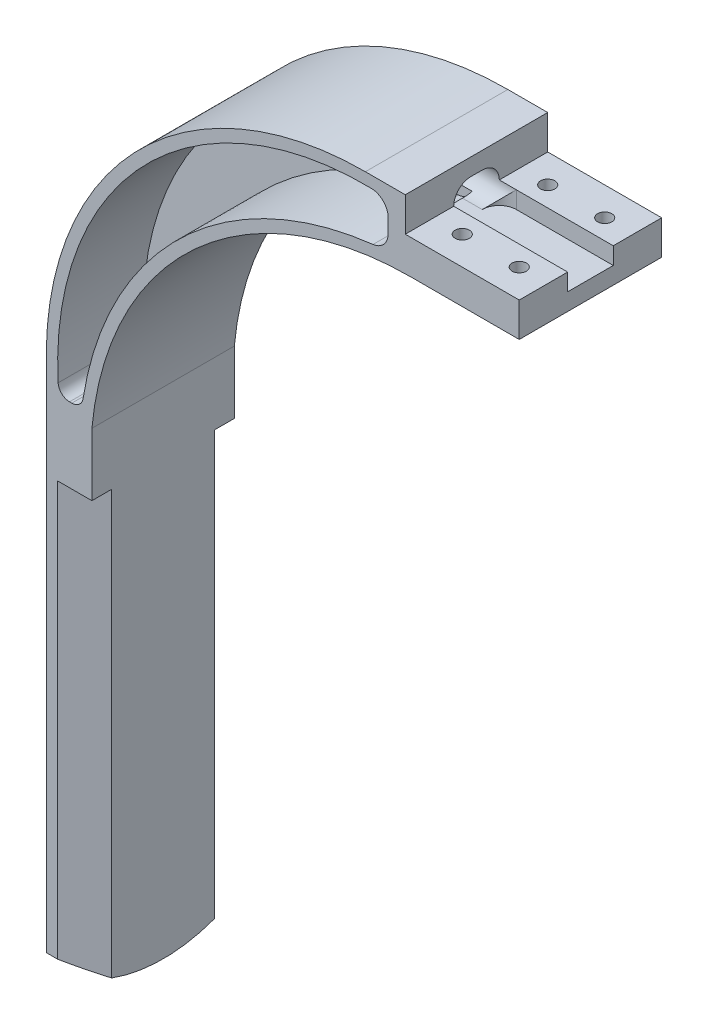
SolidWorks part; units mm, degrees
material "Сплав 2024"
ref_plane "Спереди" through (0, 0, 0) normal (0, 0, 1) x (1, 0, 0)
ref_plane "Сверху" through (0, 0, 0) normal (0, 1, 0) x (1, 0, 0)
ref_plane "Справа" through (0, 0, 0) normal (1, 0, 0) x (0, 0, -1)
sketch "Эскиз1" plane through (0, 0, 0) normal (0, 0, 1) x (1, 0, 0)
  line L0 (0, 0) -> (0, 95)
  line L1 (0, 0) -> (8, 0)
  line L2 (-20.7345, 150) -> (144.5665, 150) construction
  line L3 (83, 163.3115) -> (83, 122.0175) construction
  line L4 (8, 0) -> (8, 87)
  line L6 (83, 150) -> (56, 150)
  line L7 (83, 150) -> (83, 138)
  line L8 (83, 138) -> (64, 138)
  arc A0 (64, 138) -> (8, 87) centre (64, 81.7549) ccw
  arc A1 (56, 150) -> (0, 95) centre (56, 93.9909) ccw
  dimension "D1" = 95
  dimension "D2" = 87
  dimension "D3" = 150
  dimension "D4" = 83
  dimension "D5" = 8
  dimension "D6" = 12
  dimension "D7" = 27
  dimension "D8" = 19
extrude "Бобышка-Вытянуть1" add sketch "Эскиз1" along normal blind 25
sketch "Эскиз2" plane through (0, 0, 25) normal (0, 0, 1) x (1, 0, 0)
  line L1 (83, 150) -> (63, 150)
  line L2 (83, 150) -> (83, 144)
  line L3 (83, 144) -> (63, 144)
  line L4 (63, 150) -> (63, 144)
  dimension "D1" = 20
  dimension "D2" = 6
extrude "Вырез-Вытянуть1" cut sketch "Эскиз2" against normal through all
sketch "Эскиз5" plane through (0, 0, 0) normal (0, -1, 0) x (1, 0, 0)
  line L0 (8, 3.4641) -> (2, 0)
  line L1 (8, 25) -> (8, 0) construction
  line L3 (2, 0) -> (8, 0)
  line L4 (8, 0) -> (8, 3.4641)
  line L5 (0, 25) -> (0, 0) construction
  line L6 (8, 12.5) -> (7.5, 12.5) construction
  line L7 (8, 25) -> (8, 0) construction
  line L8 (8, 25) -> (8, 21.5359)
  line L9 (2, 25) -> (8, 25)
  line L10 (8, 21.5359) -> (2, 25)
  line L11 (0, 0) -> (8, 0) construction
  dimension "D1" = 2
  dimension "D2" = 60
extrude "Вырез-Вытянуть2" cut sketch "Эскиз5" against normal blind 76
sketch "Эскиз6" plane through (0, 0, 0) normal (-1, 0, 0) x (0, 0, 1)
  line L0 (12.5, 0) -> (12.5, 16.6862) construction
  line L1 (25, 0) -> (0, 0) construction
  line L2 (12.5, -11.9161) -> (12.5, 92.5) construction
  line L3 (10, -11.9161) -> (10, 92.5)
  line L4 (15, -11.9161) -> (15, 92.5)
  line L5 (25, 95) -> (0, 95) construction
  arc A0 (10, -11.9161) -> (15, -11.9161) centre (12.5, -11.9161) ccw
  arc A1 (15, 92.5) -> (10, 92.5) centre (12.5, 92.5) ccw
  point P7 (12.5, 40.292)
  dimension "D1" = 5
extrude "Вырез-Вытянуть4" cut sketch "Эскиз6" against normal blind 5
sketch "Эскиз3" plane through (0, 0, 25) normal (0, 0, -1) x (-1, 0, 0)
  line L0 (-60, 147.8517) -> (-60, 139.8625)
  line L1 (-63, 150) -> (-63, 144) construction
  line L2 (-6.2158, 89.0676) -> (-2.2158, 89.0676)
  arc A4 (-60, 147.8517) -> (-2.2158, 89.0676) centre (-56, 93.9909) cw
  arc A5 (-60, 139.8625) -> (-6.2158, 89.0676) centre (-64, 81.7549) cw
  arc A6 (0, 95) -> (-56, 150) centre (-56, 93.9909) ccw construction
  arc A7 (-8, 87) -> (-64, 138) centre (-64, 81.7549) ccw construction
  dimension "D1" = 2
  dimension "D2" = 2
  dimension "D3" = 3
  dimension "D4" = 4
extrude "Вырез-Вытянуть3" cut sketch "Эскиз3" along normal up to surface (15 mm away) up to face at (2.5, 46.25, 10)
fillet "Скругление3" radius 2 2 edges at (6.2158, 89.0676, 17.5) (2.2158, 89.0676, 20)
fillet "Скругление4" radius 3 2 edges at (60, 147.8517, 17.5) (60, 139.8625, 17.5)
ref_plane "Плоскость1" through (0, 10, 0) normal (0, 1, 0) x (1, 0, 0)
sketch "Эскиз8" plane through (0, 10, 0) normal (0, 1, 0) x (1, 0, 0)
  line L0 (0, -2) -> (1.5, -2)
  line L1 (0, -12.5) -> (0, 0) construction
  line L2 (1.5, -2) -> (1.5, -3)
  line L3 (3.5, -4) -> (5.5, -4)
  line L4 (5.5, -4) -> (5.5, -8)
  line L5 (5.5, -8) -> (0, -8)
  line L6 (0, -8) -> (0, -2)
  line L7 (56, 0) -> (0, 0) construction
  line L8 (2.0115, -10) -> (0, -10) construction
  line L9 (1.5, -3) -> (3.5, -3)
  line L10 (3.5, -3) -> (3.5, -4)
  line L11 (8, -25) -> (8, 0) construction
  line L12 (8, -12.5) -> (6.1534, -12.5) construction
  line L13 (3.5, -22) -> (3.5, -21)
  line L14 (1.5, -22) -> (3.5, -22)
  line L15 (0, -17) -> (0, -23)
  line L16 (5.5, -17) -> (0, -17)
  line L17 (5.5, -21) -> (5.5, -17)
  line L18 (3.5, -21) -> (5.5, -21)
  line L19 (1.5, -23) -> (1.5, -22)
  line L20 (0, -23) -> (1.5, -23)
  dimension "D1" = 2
  dimension "D2" = 2
  dimension "D3" = 4
  dimension "D4" = 1
  dimension "D5" = 1.5
  dimension "D6" = 2
  dimension "D7" = 2.5
extrude "Вырез-Вытянуть6" cut sketch "Эскиз8" along normal blind 75
sketch "Эскиз9" plane through (0, 144, 0) normal (0, 1, 0) x (1, 0, 0)
  line L0 (83, 0) -> (63, -25) construction
  line L1 (83, 0) -> (83, -25) construction
  line L2 (68, -5) -> (78, -5) construction
  line L3 (68, -5) -> (68, -20) construction
  line L4 (68, -20) -> (78, -20) construction
  line L5 (78, -5) -> (78, -20) construction
  line L6 (68, -5) -> (78, -20) construction
  line L7 (68, -20) -> (78, -5) construction
  line L8 (63, 0) -> (83, 0) construction
  point P4 (73, -12.5)
  dimension "D1" = 5
  dimension "D2" = 5
hole_wizard "Отверстие обработанное метчиком M3x0.51" positions "Эскиз11" profile "Эскиз10" tap size "M3x0.5" standard "Ansi Metric" end condition up to next
sketch "Эскиз11" plane through (0, 144, 0) normal (0, 1, 0) x (1, 0, 0)
  point P0 (68, -5)
  point P3 (78, -5)
  point P6 (78, -20)
  point P9 (68, -20)
sketch "Эскиз10" plane through (68, 144, 5) normal (1, 0, 0) x (0, 0, 1)
  line L0 (0, 0) -> (0, 6)
  line L1 (0, 6) -> (1.25, 6)
  line L2 (1.25, 6) -> (1.25, 0)
  line L5 (1.25, 0) -> (0, 0)
  line L11 (0, -6.35) -> (0, 107.95) construction
  dimension "Диаметр резьбы" = 2.5
  dimension "Глубина проходного сверла" = 6
sketch "Эскиз12" plane through (0, 0, 0) normal (-1, 0, 0) x (0, 0, 1)
  line L0 (12.5, 0) -> (12.5, 6.3491) construction
  line L1 (10, 0) -> (15, 0) construction
  line L3 (0, 3.302) -> (0, 0)
  line L4 (0, 95) -> (0, 0) construction
  line L5 (0, 0) -> (12.5, 0)
  line L6 (12.5, 0) -> (25, 0)
  line L7 (25, 0) -> (25, 3.302)
  line L8 (25, 95) -> (25, 0) construction
  arc A0 (0, 3.302) -> (25, 3.302) centre (12.5, 26.1) ccw
  dimension "D1" = 52
  dimension "D2" = 26.1
extrude "Вырез-Вытянуть7" cut sketch "Эскиз12" against normal up to next
sketch "Эскиз13" plane through (0, 144, 0) normal (0, 1, 0) x (1, 0, 0)
  line L0 (83, -12.5) -> (63, -12.5) construction
  line L1 (83, 0) -> (83, -25) construction
  line L2 (63, 0) -> (63, -25) construction
  line L4 (63, -8.5) -> (83, -8.5)
  line L5 (63, -8.5) -> (63, -16.5)
  line L6 (63, -16.5) -> (83, -16.5)
  line L7 (83, -8.5) -> (83, -16.5)
  line L8 (63, -8.5) -> (83, -16.5) construction
  line L9 (63, -16.5) -> (83, -8.5) construction
  point P6 (73, -12.5)
  dimension "D1" = 8
extrude "Вырез-Вытянуть8" cut sketch "Эскиз13" against normal blind 3
fillet "Скругление8" radius 3 2 edges at (63, 142.5, 8.5) (63, 142.5, 16.5)
sketch "Эскиз14" plane through (83, 0, 0) normal (1, 0, 0) x (0, 0, -1)
  line L0 (-12.5, 141) -> (-12.5, 154.1514) construction
  line L1 (-16.5, 141) -> (-8.5, 141) construction
  line L4 (-13.5, 144) -> (-11.5, 144) construction
  line L5 (-13.5, 147) -> (-11.5, 147)
  line L6 (-13.5, 141) -> (-11.5, 141)
  line L7 (-16.5, 141) -> (-16.5, 144) construction
  arc A0 (-13.5, 147) -> (-13.5, 141) centre (-13.5, 144) ccw
  arc A1 (-11.5, 141) -> (-11.5, 147) centre (-11.5, 144) ccw
  point P5 (-12.5, 144)
  dimension "D1" = 6
extrude "Вырез-Вытянуть9" cut sketch "Эскиз14" against normal blind 28
